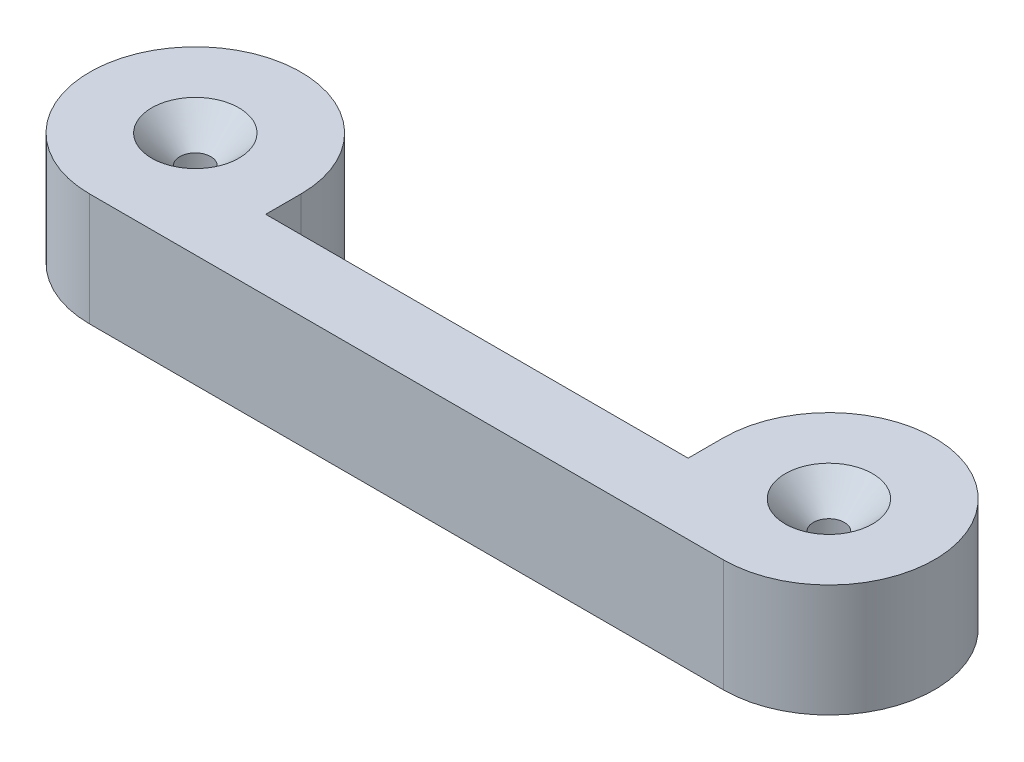
SolidWorks part; units mm, degrees
ref_plane "Plan de face" through (0, 0, 0) normal (0, 0, 1) x (1, 0, 0)
ref_plane "Plan de dessus" through (0, 0, 0) normal (0, 1, 0) x (1, 0, 0)
ref_plane "Plan de droite" through (0, 0, 0) normal (1, 0, 0) x (0, 0, -1)
sketch "Esquisse1" plane through (0, 0, 0) normal (0, 1, 0) x (1, 0, 0)
  line L0 (30, 0) -> (15, 15) construction
  line L1 (15, 0) -> (30, 0) construction
  line L2 (15, 15) -> (30, 15) construction
  line L3 (30, 0) -> (30, 15) construction
  line L4 (-15, 0) -> (-30, 0) construction
  line L5 (-15, 0) -> (-15, 15) construction
  line L6 (-15, 15) -> (-30, 15) construction
  line L7 (-30, 0) -> (-30, 15) construction
  line L8 (-15, 15) -> (-30, 0) construction
  line L9 (-15, 0) -> (15, 0) construction
  line L10 (-22.5, 0) -> (22.5, 0)
  line L13 (-15, 0) -> (-15, 5) construction
  line L16 (15, 0) -> (15, 5) construction
  line L17 (15, 15) -> (15, 5) construction
  line L18 (15, 5) -> (15, 7.5)
  line L21 (-15, 7.5) -> (-15, 5)
  line L22 (-15, 5) -> (15, 5)
  circle A0 centre (22.5, 7.5) radius 1.1
  circle A1 centre (-22.5, 7.5) radius 1.1
  circle A2 centre (22.5, 7.5) radius 7.5 construction
  arc A3 (22.5, 0) -> (15, 7.5) centre (22.5, 7.5) ccw
  arc A4 (-15, 7.5) -> (-22.5, 0) centre (-22.5, 7.5) ccw
  point P17 (0, 0)
  dimension "D1" = 2.2
  dimension "D2" = 30
  dimension "D3" = 15
  dimension "D4" = 5
extrude "Boss.-Extru.1" add sketch "Esquisse1" along normal blind 8
sketch "Esquisse2" plane through (0, 0, 0) normal (0, -1, 0) x (1, 0, 0)
  circle A0 centre (-22.5, -7.5) radius 2.6
  circle A1 centre (22.5, -7.5) radius 2.6
  dimension "D1" = 5.2
extrude "Enlèv. mat.-Extru.1" cut sketch "Esquisse2" against normal offset from surface (6 mm away) 2 up to face at (22.5, 8, -6.4)
chamfer "Chanfrein1" distance 2 angle 45 2 edges at (22.5, 8, -6.4) (-22.5, 8, -6.4)
